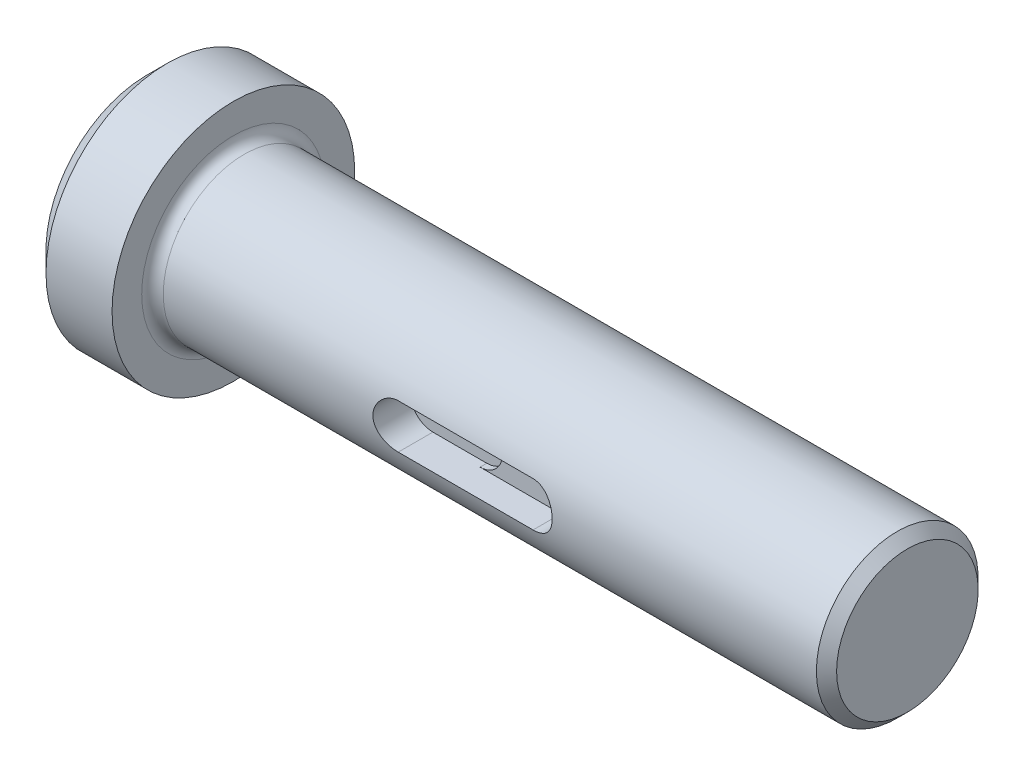
SolidWorks part; units mm, degrees
ref_plane "Front" through (0, 0, 0) normal (0, 0, 1) x (1, 0, 0)
ref_plane "Top" through (0, 0, 0) normal (0, 1, 0) x (1, 0, 0)
ref_plane "Right" through (0, 0, 0) normal (1, 0, 0) x (0, 0, -1)
sketch "Sketch2" plane through (0, 0, 0) normal (0, 0, 1) x (1, 0, 0)
  line L0 (-56.0675, 0) -> (68.4436, 0) construction
  line L1 (0, 0) -> (0, 9)
  line L2 (0, 9) -> (6.4, 9)
  line L3 (6.4, 9) -> (6.4, 6.8)
  line L4 (7.2, 6) -> (56.4, 6)
  line L5 (56.4, 6) -> (56.4, 0)
  line L6 (56.4, 0) -> (0, 0)
  arc A0 (7.2, 6) -> (6.4, 6.8) centre (7.2, 6.8) cw
revolve "Base" add sketch "Sketch2" angle 360 about L0
cosmetic thread "ThreadCosmetic1" [suppressed] parameters "b"=15, "D2"=11
chamfer "HeadChamfer" distance 1.5 angle 45 1 edges at (0, 0, 9)
ref_plane "Plane1" through (0, 0, 6) normal (0, 0, 1) x (1, 0, 0)
sketch "Sketch3" plane through (0, 0, 6) normal (0, 0, 1) x (1, 0, 0)
  line L0 (0, 0) -> (53.5043, 0) construction
  line L2 (24.4, 1.65) -> (34.4, 1.65)
  line L3 (34.4, -1.65) -> (24.4, -1.65)
  line L6 (6.4, -9) -> (6.4, 9) construction
  arc A0 (34.4, 1.65) -> (34.4, -1.65) centre (34.4, 0) cw
  arc A1 (24.4, -1.65) -> (24.4, 1.65) centre (24.4, 0) cw
  dimension "n" = 3.3
  dimension "l1" = 18
  dimension "l2" = 10
extrude "Cut-Extrude1" cut sketch "Sketch3" against normal blind 2.3
sketch "Sketch4" plane through (0, 0, 6) normal (0, 0, 1) x (1, 0, 0)
  line L4 (24.4, 1.65) -> (34.4, 1.65) construction
  line L5 (34.4, -1.65) -> (24.4, -1.65) construction
  line L6 (24.4, 1.65) -> (28.4, 1.65)
  line L7 (28.4, -1.65) -> (24.4, -1.65)
  arc A0 (28.4, -1.65) -> (28.4, 1.65) centre (28.4, 0) ccw
  arc A1 (24.4, 1.65) -> (24.4, -1.65) centre (24.4, 0) ccw construction
  arc A2 (24.4, 1.65) -> (24.4, -1.65) centre (24.4, 0) ccw
  dimension "l3" = 4
extrude "Cut-Extrude2" cut sketch "Sketch4" against normal blind 2.8
chamfer "BodyChamfer" distance 0.75 angle 45 1 edges at (56.4, 0, 6)
sketch "Sketch5" plane through (0, 0, 0) normal (0, 0, 1) x (1, 0, 0)
  line L0 (54.1917, 7.4583) -> (55.65, 7.4583)
  line L1 (55.65, 7.4583) -> (55.65, 6)
  line L2 (55.65, 6) -> (54.9208, 4.737)
  line L3 (54.9208, 4.737) -> (54.1917, 6)
  line L4 (54.1917, 6) -> (54.1917, 7.4583)
  line L6 (55.65, 6) -> (7.2, 6) construction
  line L7 (55.65, 6) -> (55.65, -6) construction
  dimension "D1" = 1.4583
revolve "Cut-Revolve10" [suppressed] cut sketch "Sketch5" angle 360 about axis through (-56.0675, 0, 0) along (1, 0, 0)
pattern_linear "LPattern10" [suppressed] count 8 along (-1, 0, 0) of bodies 104
equation "\"D1@Plane1\" = \"d@Sketch2\" / 2"
equation "\"D1@BodyChamfer\" = \"c@HeadChamfer\" / 2"
equation "\"D1@Sketch5\" = \"pitch@LPattern10\" / 1.2"
equation "\"D1@LPattern10\" = ( \"b@ThreadCosmetic1\"  - \"D1@BodyChamfer\")/  \"pitch@LPattern10\""
